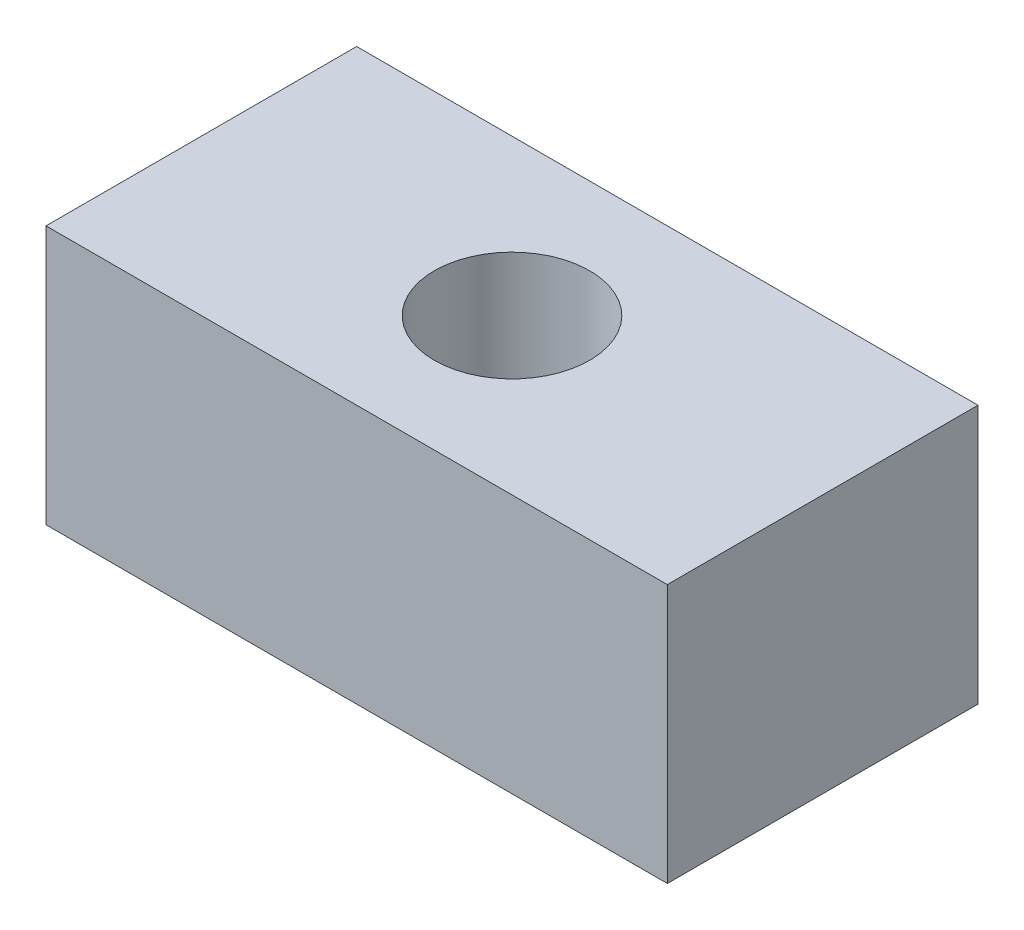
SolidWorks part; units mm, degrees
ref_plane "Front Plane" through (0, 0, 0) normal (0, 0, 1) x (1, 0, 0)
ref_plane "Top Plane" through (0, 0, 0) normal (0, 1, 0) x (1, 0, 0)
ref_plane "Right Plane" through (0, 0, 0) normal (1, 0, 0) x (0, 0, -1)
sketch "Sketch1" plane through (0, 0, 0) normal (0, 1, 0) x (1, 0, 0)
  line L5 (-6, -3) -> (6, -3)
  line L6 (-6, -3) -> (-6, 3)
  line L7 (-6, 3) -> (6, 3)
  line L8 (6, -3) -> (6, 3)
  line L9 (-6, -3) -> (6, 3) construction
  line L10 (-6, 3) -> (6, -3) construction
  circle A1 centre (0, 0) radius 1.5
  dimension "D1" = 3
  dimension "D2" = 12
  dimension "D3" = 6
extrude "Boss-Extrude1" add sketch "Sketch1" along normal blind 5
